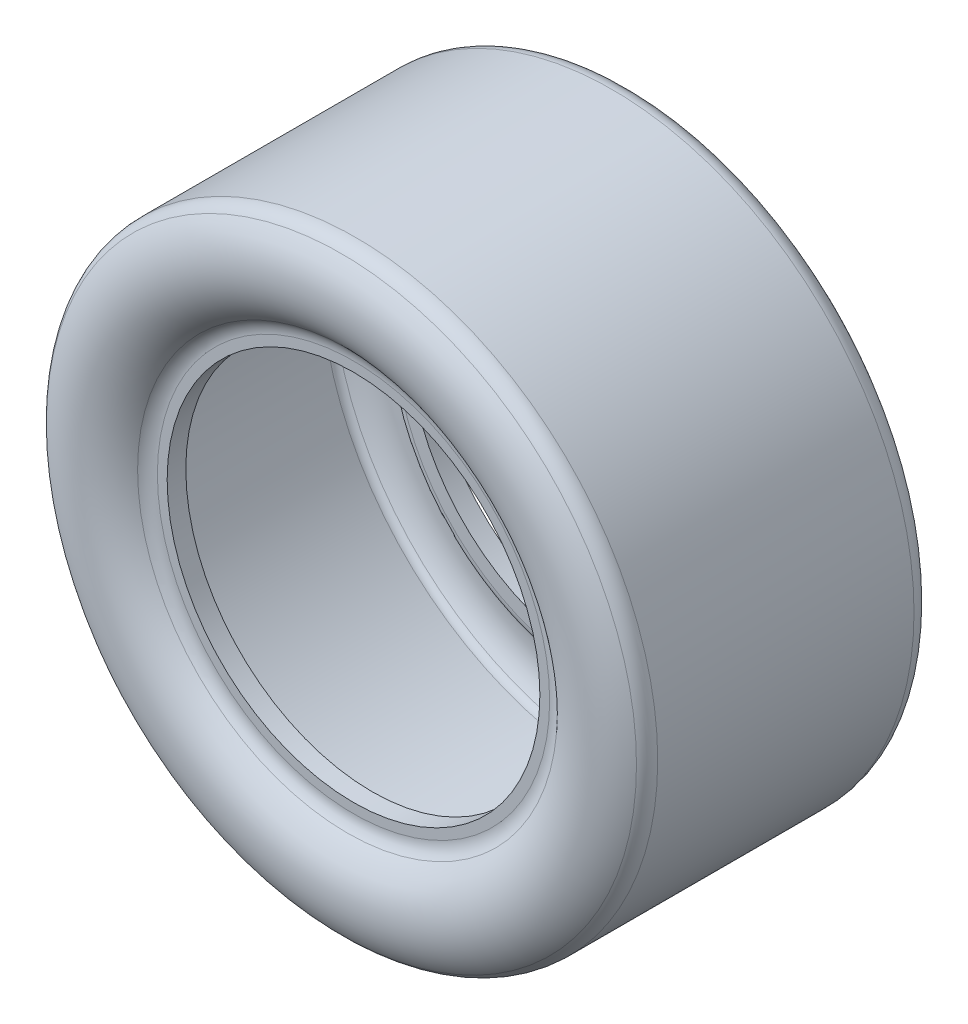
SolidWorks part; units mm, degrees
material "Tire Rubber"
ref_plane "X-Z Datum" through (0, 0, 0) normal (0, 0, 1) x (1, 0, 0)
ref_plane "X-Y Datum" through (0, 0, 0) normal (0, 1, 0) x (1, 0, 0)
ref_plane "Y-Z Plane" through (0, 0, 0) normal (1, 0, 0) x (0, 0, -1)
sketch "Sketch1" plane through (0, 0, 0) normal (1, 0, 0) x (0, 0, -1)
  line L0 (0, 0) -> (-132272.0706, 0) construction
  line L1 (-92.71, 205.74) -> (92.71, 205.74)
  line L2 (0, 0) -> (0, -132272.0706) construction
  line L4 (-88.9, 127) -> (-88.9, 139.7)
  line L5 (88.9, 127) -> (88.9, 139.7)
  line L6 (-88.9, 127) -> (-76.2, 127)
  line L8 (76.2, 127) -> (88.9, 127)
  line L9 (-76.2, 127) -> (-76.2, 136.7746)
  line L10 (76.2, 127) -> (76.2, 136.7746)
  line L11 (-86.5663, 197.8025) -> (86.5663, 197.8025)
  arc A2 (-92.71, 205.74) -> (-88.9, 139.7) centre (-64.4017, 174.2433) ccw
  arc A3 (92.71, 205.74) -> (88.9, 139.7) centre (64.4017, 174.2433) cw
  arc A4 (-91.5819, 195.3468) -> (-80.4384, 143.7974) centre (-64.4017, 174.2433) ccw
  arc A5 (-86.5663, 197.8025) -> (-91.5819, 195.3468) centre (-86.5663, 191.4525) ccw
  arc A6 (-76.2, 136.7746) -> (-80.4384, 143.7974) centre (-84.1375, 136.7746) ccw
  arc A7 (91.5819, 195.3468) -> (80.4384, 143.7974) centre (64.4017, 174.2433) cw
  arc A8 (86.5663, 197.8025) -> (91.5819, 195.3468) centre (86.5663, 191.4525) cw
  arc A9 (80.4384, 143.7974) -> (76.2, 136.7746) centre (84.1375, 136.7746) ccw
  point P7 (-106.68, 171.8041)
  dimension "D4" = 213.36
  dimension "D9" = 7.9375
  dimension "D10" = 6.35
  dimension "D11" = 7.9375
  dimension "D12" = 7.9375
  dimension "D1" = 185.42
  dimension "D2" = 411.48
  dimension "D3" = 12.7
  dimension "D5" = 177.8
  dimension "D6" = 254
  dimension "D7" = 12.7
  dimension "D8" = 7.9375
revolve "Revolve1" add sketch "Sketch1" angle 360 about L0
fillet "Fillet1" radius 12.7 4 edges at (-139.7, 0, -88.9) (-139.7, 0, 88.9) (-205.74, 0, -92.71) (-205.74, 0, 92.71)
ref_axis "Axis1" [suppressed] through (0, 0, 87.3303) along (0, 0, -1)
sketch "Sketch2" plane through (0, 0, 0) normal (0, 0, 1) x (1, 0, 0)
  circle A0 centre (0, 0) radius 205.74
  dimension "D1" = 411.48
extrude "Boss-Extrude1" [suppressed] add sketch "Sketch2" along normal mid plane 185.42
fillet "Fillet2" [suppressed] radius 25.4
sketch "Sketch3" plane through (0, 0, 0) normal (1, 0, 0) x (0, 0, -1)
  line L0 (0, 0) -> (0, 170833.7536) construction
  line L1 (0, 0) -> (-170833.7536, 0) construction
  line L2 (106.68, 205.74) -> (-106.68, 205.74)
  line L3 (-106.68, 205.74) -> (-106.68, 0)
  line L4 (106.68, 205.74) -> (106.68, 0)
  line L5 (106.68, 0) -> (-106.68, 0)
  point P7 (0, 205.74)
  dimension "D1" = 213.36
  dimension "D2" = 411.48
revolve "Revolve2" [suppressed] add sketch "Sketch3" angle 360 about L1
sketch "Sketch4" plane through (0, 0, 0) normal (0, 0, 1) x (1, 0, 0)
  line L0 (0, 0) -> (0, 101.6731)
move or copy body "Body-Move/Copy3" [suppressed] bodies to move or copy 101 parameters "D1"=0, "D2"=0, "D3"=0
move or copy body "Body-Move/Copy4" [suppressed] bodies to move or copy 106 parameters "D1"=0, "D2"=0, "D3"=0
move or copy body "Body-Move/Copy2" [suppressed] bodies to move or copy 101
move or copy body "Body-Move/Copy1" [suppressed] bodies to move or copy 101
